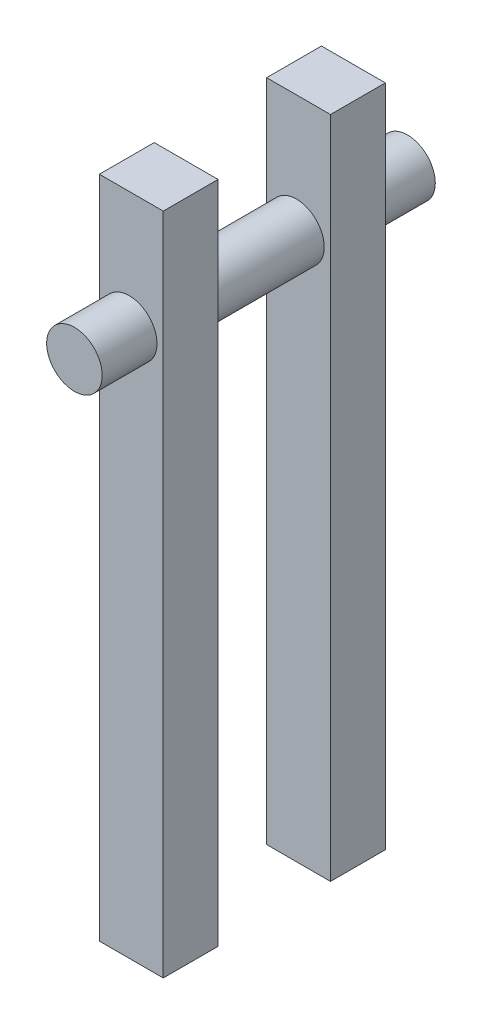
SolidWorks part; units mm, degrees
ref_plane "Front Plane" through (0, 0, 0) normal (0, 0, 1) x (1, 0, 0)
ref_plane "Top Plane" through (0, 0, 0) normal (0, 1, 0) x (1, 0, 0)
ref_plane "Right Plane" through (0, 0, 0) normal (1, 0, 0) x (0, 0, -1)
sketch "Sketch1" plane through (0, 0, 0) normal (1, 0, 0) x (0, 0, -1)
  line L0 (-32.1217, 47.1792) -> (-24.2217, 47.1792)
  line L1 (-8.0217, 47.1792) -> (-0.1217, 47.1792)
  line L2 (-8.0217, 47.1792) -> (-8.0217, -48.5208)
  line L3 (-8.0217, -48.5208) -> (-0.1217, -48.5208)
  line L4 (-0.1217, 47.1792) -> (-0.1217, -48.5208)
  line L5 (-32.1217, 47.1792) -> (-32.1217, -48.5208)
  line L6 (-32.1217, -48.5208) -> (-24.2217, -48.5208)
  line L7 (-24.2217, 47.1792) -> (-24.2217, -48.5208)
  dimension "D1" = 7.9
  dimension "D2" = 95.7
  dimension "D3" = 16.2
extrude "Boss-Extrude1" add sketch "Sketch1" along normal blind 9.2 contours L7 L6 L5 L0
extrude "Boss-Extrude2" add sketch "Sketch1<3>" along normal blind 9.2
sketch "Sketch1<3>" plane through (0, 0, 0) normal (1, 0, 0) x (0, 0, -1) same geometry as "Sketch1"
sketch "Sketch2" plane through (0, 0, 8.0217) normal (0, 0, 1) x (1, 0, 0)
  line L0 (9.2, 47.1792) -> (0, 47.1792) construction
  line L1 (9.2, 47.1792) -> (9.2, -48.5208) construction
  circle A0 centre (4.3, 30.1792) radius 4
  dimension "D1" = 8
  dimension "D2" = 17
  dimension "D3" = 4.9
extrude "Boss-Extrude3" add sketch "Sketch2" along normal blind 32 and the other way blind 16
